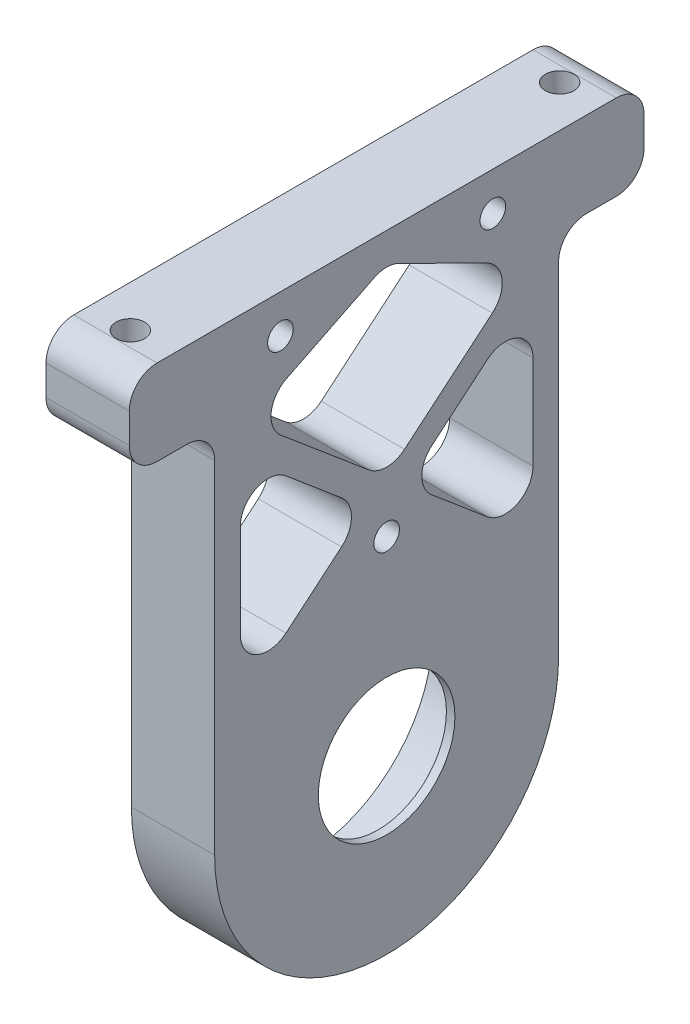
SolidWorks part; units mm, degrees
ref_plane "Front Plane" through (0, 0, 0) normal (0, 0, 1) x (1, 0, 0)
ref_plane "Top Plane" through (0, 0, 0) normal (0, 1, 0) x (1, 0, 0)
ref_plane "Right Plane" through (0, 0, 0) normal (1, 0, 0) x (0, 0, -1)
sketch "Sketch1" plane through (0, 0, 0) normal (1, 0, 0) x (0, 0, -1)
  line L0 (-20.1375, 0) -> (-20.1375, 43.3)
  line L1 (-20.1375, 43.3) -> (-30.1375, 43.3)
  line L2 (-30.1375, 43.3) -> (-30.1375, 53.3)
  line L3 (-30.1375, 53.3) -> (30.1375, 53.3)
  line L4 (30.1375, 53.3) -> (30.1375, 43.3)
  line L5 (30.1375, 43.3) -> (20.1375, 43.3)
  line L6 (20.1375, 43.3) -> (20.1375, 0)
  line L7 (-20.1375, 43.3) -> (20.1375, 9.3653)
  line L8 (20.1375, 43.3) -> (-17.1375, 11.8931)
  line L9 (-20.1375, 43.3) -> (0, 53.3)
  line L10 (0, 53.3) -> (20.1375, 43.3)
  line L11 (-16.1716, 41.9199) -> (0, 49.9505)
  line L12 (0, 49.9505) -> (16.1716, 41.9199)
  line L13 (-17.1375, 0) -> (-17.1375, 38.8108)
  line L14 (17.1375, 38.8108) -> (17.1375, 0)
  line L15 (16.1716, 41.9199) -> (-17.1375, 13.8545)
  line L16 (-17.1375, 38.8108) -> (19.171, 8.2182)
  line L17 (17.1375, 38.8108) -> (-19.1234, 8.2584)
  line L18 (-16.1716, 41.9199) -> (21.104, 10.5124)
  line L19 (19.171, 44.4471) -> (-21.0564, 10.5526) construction
  line L20 (20.1375, 43.3) -> (-20.0899, 9.4055) construction
  line L21 (-19.171, 44.4471) -> (21.104, 10.5124) construction
  line L22 (-18.8032, 40.6131) -> (0, 49.9505) construction
  line L23 (-17.1375, 0) -> (-17.1375, 43.3) construction
  line L24 (-21.104, 42.1529) -> (19.171, 8.2182) construction
  line L25 (17.1375, 43.3) -> (17.1375, 0) construction
  line L26 (0, 49.9505) -> (18.8032, 40.6131) construction
  line L27 (21.104, 42.1529) -> (-19.1234, 8.2584) construction
  line L28 (-17.1375, 44.7898) -> (-17.1375, 53.3)
  line L29 (16.1716, 45.2694) -> (16.1716, 53.3)
  line L30 (-17.1375, 50.3) -> (16.1716, 50.3)
  line L31 (-30.1375, 50.3) -> (30.1375, 50.3) construction
  line L32 (0, 24.3712) -> (0, 20.1375) construction
  circle A0 centre (0, 0) radius 15.1375
  circle A1 centre (0, 0) radius 50.8 construction
  circle A2 centre (0, 0) radius 20.1375
  circle A3 centre (0, 0) radius 53.3 construction
  circle A4 centre (0, 0) radius 8
  circle A5 centre (0, 22.2544) radius 1.5
  circle A6 centre (-12.4344, 48.8) radius 1.5
  circle A7 centre (12.4344, 48.8) radius 1.5
  point P14 (25.1375, 43.3)
  dimension "D1" = 5
  dimension "D4" = 101.6
  dimension "D5" = 30.275
  dimension "D7" = 3
  dimension "D11" = 16
  dimension "D12" = 3
  dimension "D13" = 3
  dimension "D14" = 3
  dimension "D2" = 10
  dimension "D3" = 10
  dimension "D6" = 2.5
  dimension "D8" = 1.5
  dimension "D9" = 1.5
  dimension "D10" = 3
extrude "Boss-Extrude1" add sketch "Sketch1" along normal blind 9.75 contours A3 L4 L3 | A3 L3 L2 | A2 A0 | L18 L11 L12 L15 L8 L10 L9 L7 | A2 L13 L16 L15 L7 L0 | L8 L18 L17 L14 L6 | A2 L6 L7 L14 | L18 L14 L7 L6 | A2 L14 L7 | L18 L17 L7 L14 | A2 L7 L17 L16 | L14 A2 L16 | L16 A2 L14 | L18 L15 L7 L8 | L15 L16 L8 L7 | L17 L7 L8 L16 | L18 L8 L7 L17 | L16 L15 L13 L8 | A2 L17 L16 L8 | L17 A2 L13 | A2 L8 L13 | L13 A2 L17 | L9 L30 L10 | L10 L30 L29 L3 | L28 L30 L9 L3 | A2 L16 L17 A5 | A6 L30 L28 L9 | A6 L9 L30 | A7 L10 L29 L30 | A7 L30 L10 | A4 A0 | A0 A4 region at (0, 4.6724, 19.0019) region at (0, 21.65, 19.6648) region at (0, 43.6295, 18.4312) region at (0, 48.3788, 23.7337) region at (0, 8.0901, -19.0584) region at (0, 9.9489, 17.3781) region at (0, 27.3134, 0) region at (0, 26.3327, 1.164) region at (0, 47.9234, 15.3923) region at (0, 11.6099, -18.6375) region at (0, 9.9489, -17.3781) region at (0, 14.7881, 12.3184) region at (0, 12.3432, 16.1499) region at (0, 26.3327, -1.164) region at (0, 25.3519, 0) region at (0, 19.3488, 9.4381) region at (0, 49.4913, 9.488) region at (0, 51.907, 9.9713) region at (0, 12.875, -18.8771) region at (0, 12.3432, -16.1499) region at (0, 19.3488, -9.4381) region at (0, 14.7881, -12.3184) region at (0, 21.449, 4.74) region at (0, 21.6665, 3.002) region at (0, 21.449, -4.74) region at (0, 51.3, 0) region at (0, 48.425, -23.3174) region at (0, 51.9148, -9.4805) region at (0, 49.4913, -9.488) region at (0, 48.0354, -14.8464) region at (0, 0, 14.7093) region at (0, 0, 0)
sketch "Sketch3" plane through (0, 53.3, 0) normal (0, 1, 0) x (1, 0, 0)
  line L0 (9.75, 30.1375) -> (0, 20.1375) construction
  line L1 (0, -30.1375) -> (0, 30.1375) construction
  line L2 (0, 0) -> (9.75, 0) construction
  line L3 (9.75, -30.1375) -> (9.75, 30.1375) construction
  circle A0 centre (4.875, 25.1375) radius 1.675
  circle A1 centre (4.875, -25.1375) radius 1.675
  dimension "D1" = 3.35
extrude "Cut-Extrude1" cut sketch "Sketch3" against normal up to surface (10 mm away) up to face at (4.875, 43.3, -25.1375)
extrude "Cut-Extrude2" cut sketch "Sketch1<4>" along normal up to next contours A4 region at (0, 0, 0)
sketch "Sketch1<4>" plane through (0, 0, 0) normal (1, 0, 0) x (0, 0, -1) same geometry as "Sketch1"
fillet "Fillet1" radius 3.25 16 edges at (4.875, 28.2941, 0) (4.875, 13.8545, 17.1375) (4.875, 49.9505, 0) (4.875, 38.8108, -17.1375) (4.875, 13.8545, -17.1375) (4.875, 26.3327, 2.3279) (4.875, 41.9199, -16.1716) (4.875, 43.3, 20.1375) (4.875, 41.9199, 16.1716) (4.875, 43.3, -20.1375) (4.875, 38.8108, 17.1375) (4.875, 53.3, 30.1375) (4.875, 43.3, 30.1375) (4.875, 53.3, -30.1375) (4.875, 43.3, -30.1375) (4.875, 26.3327, -2.3279)
extrude "Cut-Extrude3" cut sketch "Sketch1<5>" along normal offset from surface (8.75 mm away) 1 contours A0 A4 region at (0, 0, 14.7093) up to face at (9.75, 0, -8)
sketch "Sketch1<5>" plane through (0, 0, 0) normal (1, 0, 0) x (0, 0, -1) same geometry as "Sketch1"
